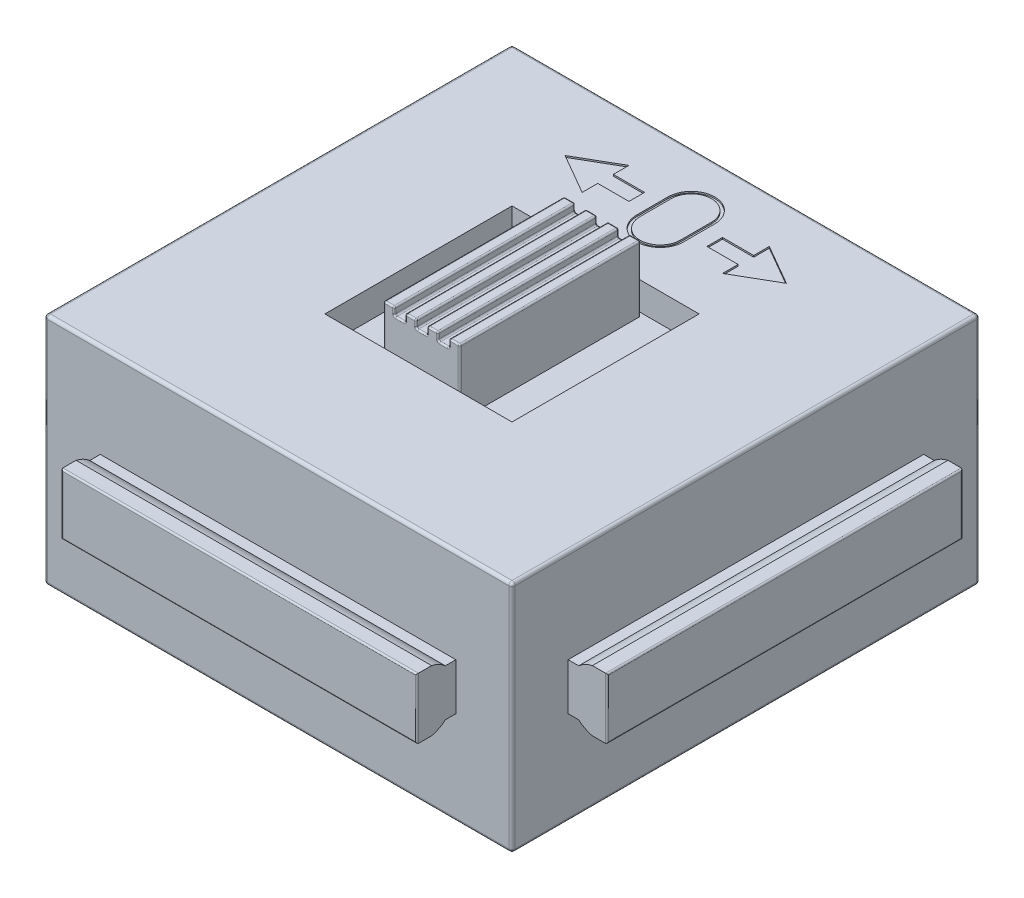
SolidWorks part; units mm, degrees
ref_plane "前视基准面" through (0, 0, 0) normal (0, 0, 1) x (1, 0, 0)
ref_plane "上视基准面" through (0, 0, 0) normal (0, 1, 0) x (1, 0, 0)
ref_plane "右视基准面" through (0, 0, 0) normal (1, 0, 0) x (0, 0, -1)
sketch "草图1" plane through (0, 0, 0) normal (0, 1, 0) x (1, 0, 0)
  line L0 (15, 15) -> (15, -15)
  line L1 (15, 15) -> (-15, 15)
  line L2 (15, -15) -> (-15, -15)
  line L3 (-15, 15) -> (-15, -15)
  line L4 (15, 15) -> (-15, -15) construction
  line L5 (15, -15) -> (-15, 15) construction
  point P1 (0, 0)
  dimension "D1" = 30
  dimension "D2" = 30
extrude "凸台-拉伸1" add sketch "草图1" along normal blind 15
sketch "草图2" plane through (15, 0, 0) normal (1, 0, 0) x (0, 0, -1)
  line L0 (-15, 7.5) -> (-17, 7.5) construction
  line L1 (-15, 15) -> (-15, 0) construction
  line L2 (-17, 7.5) -> (-17.5, 7.5) construction
  line L3 (-15, 9) -> (-15, 6)
  line L4 (-15, 6) -> (-15.6771, 6)
  line L5 (-17.5, 9.45) -> (-17.5, 5.55)
  line L6 (-17.5, 5.55) -> (-16.5556, 5.55)
  line L7 (-15, 9) -> (-15.6771, 9)
  line L8 (-17.5, 9.45) -> (-16.5556, 9.45)
  arc A0 (-16.5556, 5.55) -> (-15.6771, 6) centre (-17, 7.5) ccw
  arc A1 (-16.5556, 9.45) -> (-15.6771, 9) centre (-17, 7.5) cw
  dimension "D5" = 2
  dimension "D1" = 2
  dimension "D2" = 0.5
  dimension "D3" = 1.5
  dimension "D4" = 1.95
extrude "凸台-拉伸2" add sketch "草图2" against normal blind 22.8 from offset 3.6 offset against normal yes
mirror "镜向1" about plane through (0, 0, 0) normal (0, 0, 1) of "凸台-拉伸2"
sketch "草图3" plane through (0, 0, 15) normal (0, 0, 1) x (1, 0, 0)
  line L0 (15, 7.5) -> (17, 7.5) construction
  line L1 (15, 15) -> (15, 0) construction
  line L2 (17, 7.5) -> (17.5, 7.5) construction
  line L3 (15, 6) -> (15, 9)
  line L4 (15, 9) -> (15.6771, 9)
  line L5 (17.5, 5.55) -> (17.5, 9.45)
  line L6 (17.5, 9.45) -> (16.5556, 9.45)
  line L7 (17.5, 5.55) -> (16.5556, 5.55)
  line L8 (15, 6) -> (15.6771, 6)
  arc A0 (16.5556, 9.45) -> (15.6771, 9) centre (17, 7.5) ccw
  arc A1 (16.5556, 5.55) -> (15.6771, 6) centre (17, 7.5) cw
  dimension "D5" = 2
  dimension "D1" = 2
  dimension "D2" = 0.5
  dimension "D3" = 1.5
  dimension "D4" = 1.95
extrude "凸台-拉伸3" add sketch "草图3" against normal blind 22.8 from offset 3.6 offset against normal yes
sketch "草图4" plane through (0, 15, 0) normal (0, 1, 0) x (1, 0, 0)
  line L0 (6, 6) -> (6, -6)
  line L1 (6, 6) -> (-6, 6)
  line L2 (6, -6) -> (-6, -6)
  line L3 (-6, 6) -> (-6, -6)
  line L4 (6, 6) -> (-6, -6) construction
  line L5 (6, -6) -> (-6, 6) construction
  point P1 (0, 0)
  dimension "D1" = 12
  dimension "D2" = 12
extrude "切除-拉伸1" cut sketch "草图4" against normal blind 1.8
sketch "草图5" plane through (0, 13.2, 0) normal (0, 1, 0) x (1, 0, 0)
  line L0 (2.45, 5.8) -> (2.45, -5.8)
  line L1 (2.45, 5.8) -> (-2.45, 5.8)
  line L2 (2.45, -5.8) -> (-2.45, -5.8)
  line L3 (-2.45, 5.8) -> (-2.45, -5.8)
  line L4 (2.45, 5.8) -> (-2.45, -5.8) construction
  line L5 (2.45, -5.8) -> (-2.45, 5.8) construction
  point P1 (0, 0)
  dimension "D1" = 11.6
  dimension "D2" = 4.9
extrude "凸台-拉伸4" add sketch "草图5" along normal blind 4.2
sketch "草图6" plane through (0, 0, 5.8) normal (0, 0, 1) x (1, 0, 0)
  line L0 (-2.45, 17.4) -> (-1.75, 17.4) construction
  line L1 (-2.45, 17.4) -> (2.45, 17.4) construction
  line L2 (-1.75, 17.4) -> (-1.05, 17.4)
  line L3 (-1.05, 17.4) -> (-0.35, 17.4) construction
  line L4 (-0.35, 17.4) -> (0.35, 17.4)
  line L5 (0.35, 17.4) -> (1.05, 17.4) construction
  line L6 (1.05, 17.4) -> (1.75, 17.4)
  line L7 (1.75, 17.4) -> (2.45, 17.4) construction
  line L8 (-1.75, 17.4) -> (-1.75, 16.9)
  line L9 (-1.75, 16.9) -> (-1.05, 16.9)
  line L10 (-1.05, 16.9) -> (-1.05, 17.4)
  line L11 (-0.35, 17.4) -> (-0.35, 16.9)
  line L12 (-0.35, 16.9) -> (0.35, 16.9)
  line L13 (0.35, 16.9) -> (0.35, 17.4)
  line L14 (1.05, 17.4) -> (1.05, 16.9)
  line L15 (1.05, 16.9) -> (1.75, 16.9)
  line L16 (1.75, 16.9) -> (1.75, 17.4)
  dimension "D1" = 0.7
  dimension "D2" = 0.7
  dimension "D3" = 0.7
  dimension "D4" = 0.7
  dimension "D5" = 0.7
  dimension "D6" = 0.7
  dimension "D7" = 0.5
  dimension "D8" = 0.5
  dimension "D9" = 0.5
extrude "切除-拉伸2" cut sketch "草图6" against normal up to next
sketch "草图7" plane through (0, 15, 0) normal (0, 1, 0) x (1, 0, 0)
  line L0 (0, 15) -> (0, 10.5) construction
  line L1 (-11.4, 15) -> (11.4, 15) construction
  line L2 (1.5, 11.5) -> (-1.5, 11.5) construction
  line L3 (1.5, 11.5) -> (1.5, 9.5)
  line L4 (-1.5, 11.5) -> (-1.5, 9.5)
  line L5 (1.5, 9.5) -> (-1.5, 9.5) construction
  line L6 (1.5, 11.5) -> (-1.5, 9.5) construction
  line L7 (-1.5, 11.5) -> (1.5, 9.5) construction
  line L8 (-1.3, 11.5) -> (-1.3, 9.5)
  line L9 (1.3, 11.5) -> (1.3, 9.5)
  line L10 (0, 10.5) -> (-3.5, 10.5) construction
  line L11 (-2.5, 11) -> (-2.5, 10)
  line L12 (-2.5, 11) -> (-4.5, 11)
  line L13 (-2.5, 10) -> (-4.5, 10)
  line L14 (-4.5, 11) -> (-4.5, 10) construction
  line L15 (-2.5, 11) -> (-4.5, 10) construction
  line L16 (-2.5, 10) -> (-4.5, 11) construction
  line L17 (-4.5, 11) -> (-4.5, 12)
  line L18 (-4.5, 12) -> (-7.0981, 10.5)
  line L19 (-4.5, 10) -> (-4.5, 9)
  line L20 (-4.5, 9) -> (-7.0981, 10.5)
  line L21 (4.5, 11) -> (4.5, 12)
  line L22 (2.5, 11) -> (4.5, 11)
  line L23 (2.5, 11) -> (2.5, 10)
  line L24 (2.5, 10) -> (4.5, 10)
  line L25 (4.5, 10) -> (4.5, 9)
  line L26 (4.5, 9) -> (7.0981, 10.5)
  line L27 (4.5, 12) -> (7.0981, 10.5)
  line L28 (4.5, 11) -> (4.5, 10) construction
  arc A0 (1.5, 11.5) -> (-1.5, 11.5) centre (0, 11.5) ccw
  arc A1 (-1.5, 9.5) -> (1.5, 9.5) centre (0, 9.5) ccw
  arc A2 (1.3, 11.5) -> (-1.3, 11.5) centre (0, 11.5) ccw
  arc A3 (-1.3, 9.5) -> (1.3, 9.5) centre (0, 9.5) ccw
  dimension "D1" = 4.5
  dimension "D2" = 3
  dimension "D3" = 2
  dimension "D5" = 3.5
  dimension "D6" = 2
  dimension "D7" = 1
  dimension "D8" = 1
  dimension "D9" = 1
  dimension "D10" = 60
  dimension "D11" = 60
  dimension "D4" = 0.2
extrude "切除-拉伸3" cut sketch "草图7" against normal blind 0.1
sketch "草图8" plane through (0, 0, 0) normal (0, -1, 0) x (1, 0, 0)
  line L0 (-15, 15) -> (-15, 10) construction
  line L1 (-15, -15) -> (-15, 15) construction
  line L2 (-15, 10) -> (-10, 10) construction
  line L3 (-10, 10) -> (-5, 10) construction
  line L4 (-5, 10) -> (-5, -15) construction
  line L5 (15, -15) -> (-15, -15) construction
  line L6 (-15, -15) -> (-15, -10) construction
  line L7 (-15, -10) -> (-10, -10) construction
  line L8 (-10, -10) -> (-7, -10) construction
  line L9 (-13, 10) -> (-13, -10)
  line L10 (-7, 10) -> (-7, -10)
  line L11 (-12, 7.7639) -> (-12, -7.7639)
  line L12 (-8, 7.7639) -> (-8, -7.7639)
  line L13 (-3, 10) -> (-3, -10)
  line L14 (-2, 7.7639) -> (-2, -7.7639)
  line L15 (3, 10) -> (3, -10)
  line L16 (2, 7.7639) -> (2, -7.7639)
  line L18 (-12, 10) -> (-12, -10) construction
  line L19 (-8, 10) -> (-8, -10) construction
  arc A0 (-7, 10) -> (-13, 10) centre (-10, 10) ccw
  arc A1 (-13, -10) -> (-7, -10) centre (-10, -10) ccw
  arc A4 (3, -10) -> (-3, -10) centre (0, -10) cw
  arc A7 (-3, 10) -> (3, 10) centre (0, 10) cw
  arc A8 (-8, -7.7639) -> (-12, -7.7639) centre (-10, -10) ccw
  arc A9 (-2, 7.7639) -> (2, 7.7639) centre (0, 10) ccw
  arc A10 (2, -7.7639) -> (-2, -7.7639) centre (0, -10) ccw
  arc A11 (-12, 7.7639) -> (-8, 7.7639) centre (-10, 10) ccw
  arc A12 (-8, 10) -> (-12, 10) centre (-10, 10) ccw construction
  arc A13 (-12, -10) -> (-8, -10) centre (-10, -10) ccw construction
  dimension "D4" = 6
  dimension "D7" = 6
  dimension "D9" = 3
  dimension "D10" = 3
  dimension "D11" = 3
  dimension "D12" = 3
  dimension "D1" = 5
  dimension "D2" = 5
  dimension "D3" = 5
  dimension "D5" = 5
  dimension "D6" = 5
  dimension "D8" = 1
extrude "切除-拉伸5" cut sketch "草图8" against normal blind 0.1
sketch "草图9" plane through (0, 0.1, 0) normal (0, -1, 0) x (1, 0, 0)
  circle A0 centre (-10, 10) radius 2.5
  circle A1 centre (0, 10) radius 2.5
  circle A2 centre (-10, -10) radius 2.5
  circle A3 centre (0, -10) radius 2.5
  dimension "D1" = 5
  dimension "D2" = 5
  dimension "D3" = 5
  dimension "D4" = 5
extrude "凸台-拉伸5" add sketch "草图9" along normal blind 0.1
sketch "草图10" plane through (0, 0, 0) normal (0, -1, 0) x (1, 0, 0)
  circle A0 centre (-10, 10) radius 1.25
  circle A1 centre (0, 10) radius 1.25
  circle A2 centre (-10, -10) radius 1.25
  circle A3 centre (0, -10) radius 1.25
  dimension "D1" = 2.5
  dimension "D2" = 2.5
  dimension "D3" = 2.5
  dimension "D4" = 2.5
extrude "切除-拉伸6" cut sketch "草图10" against normal blind 7.5
sketch "草图11" plane through (0, 0, 0) normal (0, -1, 0) x (1, 0, 0)
  line L0 (-1.25, 5.7639) -> (-1.25, -5.4475) construction
  line L1 (-11.25, 4.7639) -> (-11.25, -5.5177) construction
  line L2 (-2, 7.7639) -> (-2, -7.7639) construction
  line L3 (-12, 7.7639) -> (-12, -7.7639) construction
  text T0 "Batterie" font "Calibri" height in points 6
  text T1 "Motor" font "Calibri" height in points 6
  dimension "D1" = 2
  dimension "D2" = 3
  dimension "D3" = 0.75
  dimension "D4" = 0.75
extrude "切除-拉伸7" cut sketch "草图11" against normal blind 0.1
fillet "圆角1" radius 0.2 12 edges at (-15, 15, 0) (-15, 0, 0) (-15, 7.5, -15) (0, 15, -15) (0, 0, -15) (15, 7.5, -15) (15, 15, 0) (15, 0, 0) (0, 0, 15) (15, 7.5, 15) (0, 15, 15) (-15, 7.5, 15)
fillet "圆角3" radius 0.1 44 edges at (-1.05, 17.15, 5.8) (-1.05, 17.15, -5.8) (0.35, 17.15, 5.8) (0.35, 17.15, -5.8) (1.75, 17.15, 5.8) (1.75, 17.15, -5.8) (1.05, 17.15, 5.8) (1.05, 17.15, -5.8) (-0.35, 17.15, 5.8) (-0.35, 17.15, -5.8) (-1.75, 17.15, 5.8) (-1.75, 17.15, -5.8) (-2.1, 17.4, 5.8) (-2.45, 17.4, 0) (-2.1, 17.4, -5.8) (-1.75, 17.4, 0) (-1.05, 16.9, 0) (-1.4, 16.9, 5.8) (-1.75, 16.9, 0) (-1.4, 16.9, -5.8) (-0.7, 17.4, 5.8) (-1.05, 17.4, 0) (-0.7, 17.4, -5.8) (-0.35, 17.4, 0) (0.35, 16.9, 0) (0, 16.9, 5.8) (-0.35, 16.9, 0) (0, 16.9, -5.8) (0.7, 17.4, 5.8) (0.35, 17.4, 0) (0.7, 17.4, -5.8) (1.05, 17.4, 0) (1.75, 16.9, 0) (1.4, 16.9, 5.8) (1.05, 16.9, 0) (1.4, 16.9, -5.8) (2.1, 17.4, -5.8) (2.45, 17.4, 0) (2.1, 17.4, 5.8) (1.75, 17.4, 0) (2.45, 15.3, -5.8) (2.45, 15.3, 5.8) (-2.45, 15.3, -5.8) (-2.45, 15.3, 5.8)
fillet "圆角4" radius 0.1 12 edges at (0, 5.55, 17.5) (-11.4, 7.5, 17.5) (0, 9.45, 17.5) (11.4, 7.5, 17.5) (17.5, 9.45, 0) (17.5, 7.5, -11.4) (17.5, 5.55, 0) (17.5, 7.5, 11.4) (0, 9.45, -17.5) (-11.4, 7.5, -17.5) (0, 5.55, -17.5) (11.4, 7.5, -17.5)
fillet "圆角5" radius 0.1 8 edges at (0, 0, 7.5) (0, 0, 8.75) (-10, 0, 7.5) (-10, 0, 8.75) (-10, 0, -12.5) (-10, 0, -11.25) (0, 0, -12.5) (0, 0, -11.25)
